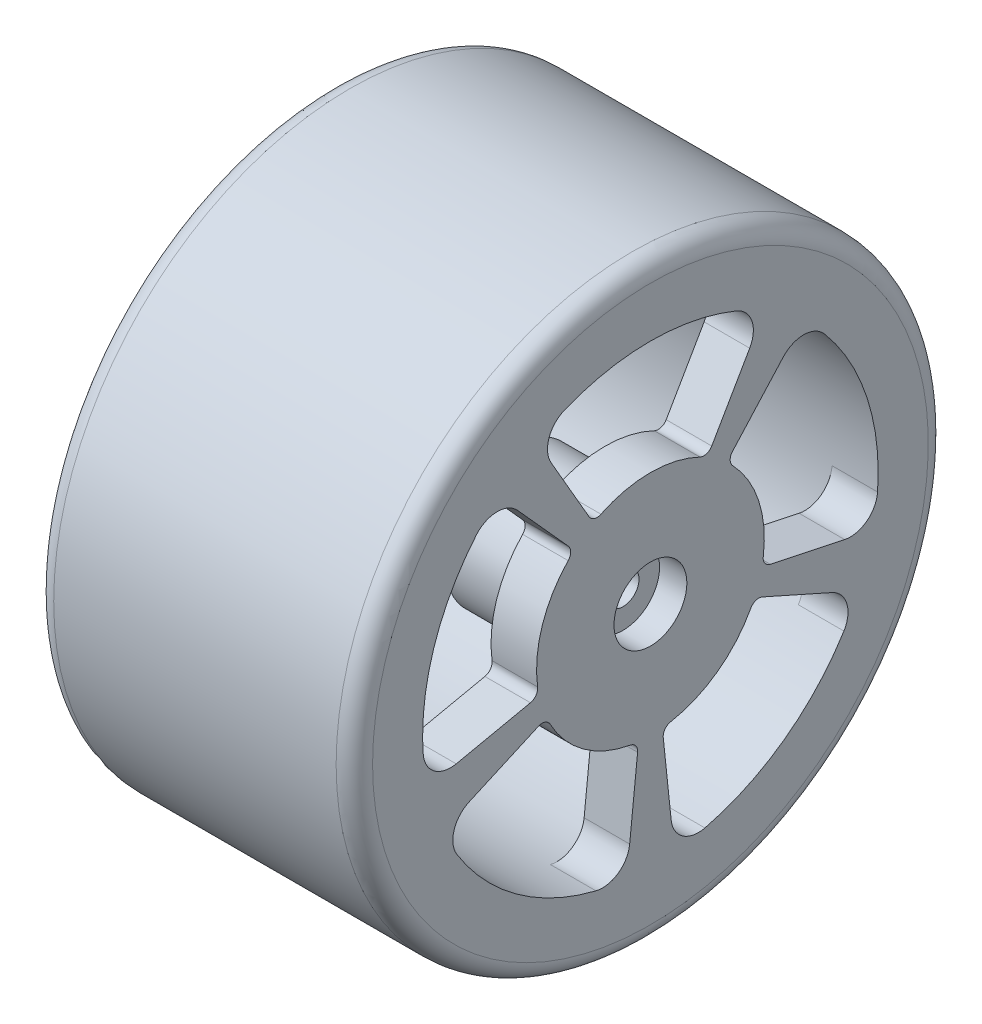
SolidWorks part; units mm, degrees
ref_plane "前视基准面" through (0, 0, 0) normal (0, 0, 1) x (1, 0, 0)
ref_plane "上视基准面" through (0, 0, 0) normal (0, 1, 0) x (1, 0, 0)
ref_plane "右视基准面" through (0, 0, 0) normal (1, 0, 0) x (0, 0, -1)
sketch "草图2" plane through (0, 0, 0) normal (0, 0, 1) x (1, 0, 0)
  line L0 (-26.7907, 0) -> (33.2791, 0) construction
  line L1 (0, 0) -> (0, 28)
  line L2 (0, 28) -> (-35, 28)
  line L3 (-35, 28) -> (-35, 25)
  line L4 (-35, 25) -> (-5, 25)
  line L5 (-5, 25) -> (-5, 0)
  line L6 (-5, 0) -> (0, 0)
  dimension "D1" = 3
  dimension "D2" = 5
  dimension "D3" = 28
  dimension "D4" = 35
revolve "旋转1" add sketch "草图2" angle 360 about L0
sketch "草图3" plane through (0, 0, 0) normal (1, 0, 0) x (0, 0, -1)
  line L0 (0, 0) -> (0, 29.841) construction
  line L1 (6.25, 10.8253) -> (12.5, 21.6506)
  line L2 (-6.25, 10.8253) -> (-12.5, 21.6506)
  line L3 (8.3641, 9.2893) -> (16.7283, 18.5786)
  line L4 (12.2268, -2.5989) -> (24.4537, -5.1978)
  line L5 (11.4193, -5.0842) -> (22.8386, -10.1684)
  line L6 (1.3066, -12.4315) -> (2.6132, -24.863)
  line L7 (-1.3066, -12.4315) -> (-2.6132, -24.863)
  line L8 (-11.4193, -5.0842) -> (-22.8386, -10.1684)
  line L9 (-12.2268, -2.5989) -> (-24.4537, -5.1978)
  line L10 (-8.3641, 9.2893) -> (-16.7283, 18.5786)
  arc A0 (-11.4193, -5.0842) -> (-1.3066, -12.4315) centre (0, 0) ccw
  arc A1 (-22.8386, -10.1684) -> (-2.6132, -24.863) centre (0, 0) ccw
  arc A2 (1.3066, -12.4315) -> (11.4193, -5.0842) centre (0, 0) ccw
  arc A3 (2.6132, -24.863) -> (22.8386, -10.1684) centre (0, 0) ccw
  arc A4 (12.2268, -2.5989) -> (8.3641, 9.2893) centre (0, 0) ccw
  arc A5 (24.4537, -5.1978) -> (16.7283, 18.5786) centre (0, 0) ccw
  arc A6 (12.5, 21.6506) -> (-12.5, 21.6506) centre (0, 0) ccw
  arc A7 (6.25, 10.8253) -> (-6.25, 10.8253) centre (0, 0) ccw
  arc A8 (-16.7283, 18.5786) -> (-24.4537, -5.1978) centre (0, 0) ccw
  arc A9 (-8.3641, 9.2893) -> (-12.2268, -2.5989) centre (0, 0) ccw
  circle A10 centre (0, 0) radius 1.75
  point P28 (0, 0)
  dimension "D1" = 30
  dimension "D2" = 30
  dimension "D3" = 5
extrude "切除-拉伸1" cut sketch "草图3" against normal blind 10
fillet "圆角3" radius 3 10 edges at (-2.5, 18.5786, 16.7283) (-2.5, 18.5786, -16.7283) (-2.5, 21.6506, -12.5) (-2.5, -10.1684, -22.8386) (-2.5, -5.1978, -24.4537) (-2.5, -24.863, 2.6132) (-2.5, 21.6506, 12.5) (-2.5, -10.1684, 22.8386) (-2.5, -24.863, -2.6132) (-2.5, -5.1978, 24.4537)
fillet "圆角4" radius 1 10 edges at (-2.5, -5.0842, -11.4193) (-2.5, -12.4315, 1.3066) (-2.5, -5.0842, 11.4193) (-2.5, 10.8253, -6.25) (-2.5, -12.4315, -1.3066) (-2.5, 9.2893, -8.3641) (-2.5, -2.5989, -12.2268) (-2.5, 10.8253, 6.25) (-2.5, 9.2893, 8.3641) (-2.5, -2.5989, 12.2268)
sketch "草图4" plane through (-5, 0, 0) normal (-1, 0, 0) x (0, 0, 1)
  line L1 (2.8545, 5.0185) -> (-2.9188, 4.9813)
  line L2 (-2.9188, 4.9813) -> (-5.7734, -0.0371)
  line L3 (-5.7734, -0.0371) -> (-2.8545, -5.0185)
  line L4 (-2.8545, -5.0185) -> (2.9188, -4.9813)
  line L5 (2.9188, -4.9813) -> (5.7734, 0.0371)
  line L6 (5.7734, 0.0371) -> (2.8545, 5.0185)
  circle A0 centre (0, 0) radius 7.5
  circle A1 centre (0, 0) radius 5 construction
  dimension "D1" = 10
extrude "凸台-拉伸1" add sketch "草图4" along normal blind 10
sketch "草图5" plane through (0, 0, 0) normal (1, 0, 0) x (0, 0, -1)
  circle A0 centre (0, 0) radius 4
extrude "切除-拉伸2" cut sketch "草图5" against normal blind 3
sketch "草图6" plane through (0, 0, 0) normal (1, 0, 0) x (0, 0, -1)
  circle A0 centre (0, 0) radius 28
  circle A1 centre (0, 0) radius 32.5
extrude "凸台-拉伸2" add sketch "草图6" against normal up to surface (35 mm away) up to face at (-35, 0, 25)
fillet "圆角5" radius 2 2 edges at (0, 0, -32.5) (-35, 0, -32.5)
